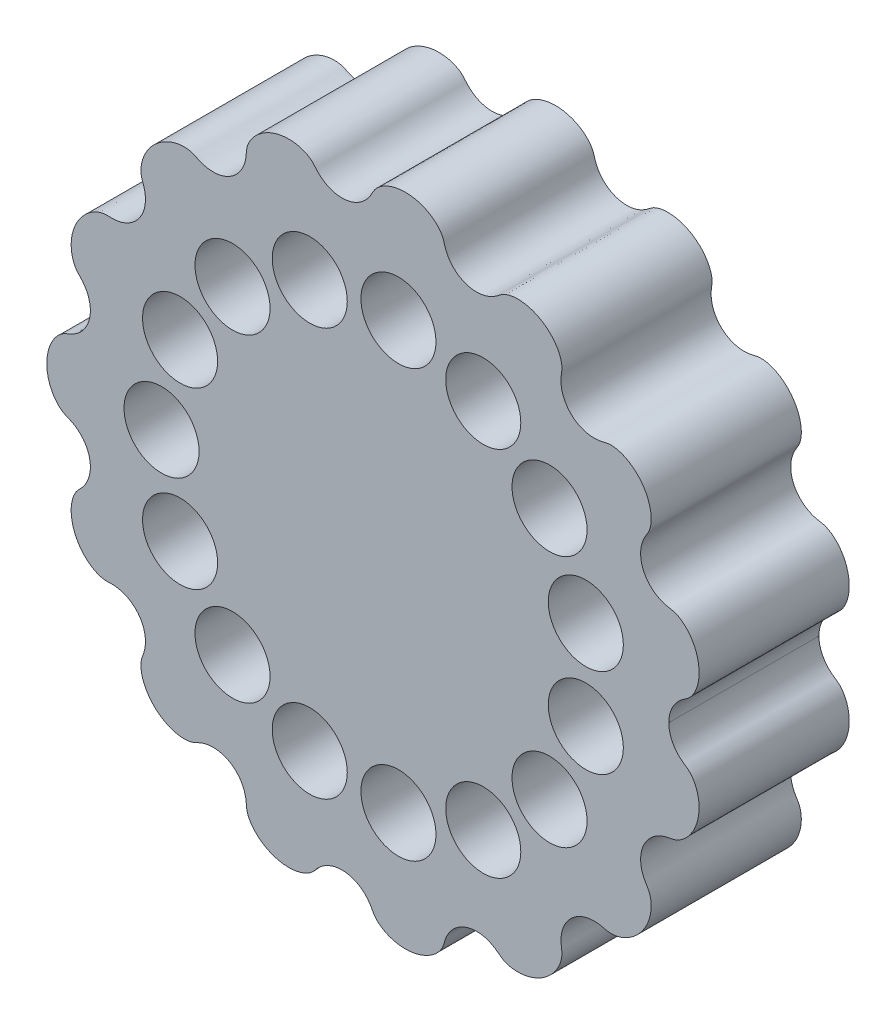
SolidWorks part; units mm, degrees
material "ABS"
ref_plane "Front Plane" through (0, 0, 0) normal (0, 0, 1) x (1, 0, 0)
ref_plane "Top Plane" through (0, 0, 0) normal (0, 1, 0) x (1, 0, 0)
ref_plane "Right Plane" through (0, 0, 0) normal (1, 0, 0) x (0, 0, -1)
sketch "Sketch2" plane through (0, 0, 0) normal (0, 0, 1) x (1, 0, 0)
  line L0 (0, 0) -> (18.3781, 0) construction
  line L1 (0, 0) -> (-12.7, 0) construction
  line L6 (0, 0) -> (-26.7529, 0) construction
  circle A0 centre (0, 0) radius 9
  circle A1 centre (-12.7, 0) radius 2.2225
  circle A10 centre (-11.602, 5.1656) radius 2.2225
  circle A11 centre (-8.498, 9.4379) radius 2.2225
  circle A12 centre (-3.9245, 12.0784) radius 2.2225
  circle A13 centre (1.3275, 12.6304) radius 2.2225
  circle A14 centre (6.35, 10.9985) radius 2.2225
  circle A15 centre (10.2745, 7.4649) radius 2.2225
  circle A16 centre (12.4225, 2.6405) radius 2.2225
  circle A17 centre (12.4225, -2.6405) radius 2.2225
  circle A18 centre (10.2745, -7.4649) radius 2.2225
  circle A19 centre (6.35, -10.9985) radius 2.2225
  circle A20 centre (1.3275, -12.6304) radius 2.2225
  circle A21 centre (-3.9245, -12.0784) radius 2.2225
  circle A22 centre (-8.498, -9.4379) radius 2.2225
  circle A23 centre (-11.602, -5.1656) radius 2.2225
  spline S0 degree 4 poles (18.7633, 4.8586) (18.8566, 4.6949) (19.0126, 4.3502) (19.1295, 3.8883) (19.146, 3.3193) (19.0772, 2.8818) (18.9864, 2.5766) (18.8762, 2.3288) (18.7622, 2.1358) (18.6445, 1.9821) (18.5309, 1.8645) (18.4127, 1.7724) (18.2984, 1.6976) (18.1631, 1.6053) (18.0131, 1.4864) (17.8313, 1.3119) (17.6678, 1.103) (17.5417, 0.8858) (17.4501, 0.6688) (17.4009, 0.5099) (17.3699, 0.3735) (17.3511, 0.2546) (17.3405, 0.1491) (17.3351, 0.0404) (17.335, -0.0379) (17.3404, -0.1482) (17.3511, -0.2558) (17.3711, -0.3808) (17.4057, -0.5292) (17.4608, -0.6993) (17.5431, -0.8835) (17.6435, -1.0585) (17.7605, -1.2214) (17.8868, -1.3648) (18.0188, -1.4893) (18.152, -1.5968) (18.284, -1.6887) (18.4068, -1.7677) (18.5101, -1.8484) (18.6114, -1.9469) (18.7103, -2.0649) (18.8119, -2.2151) (18.9788, -2.5318) (19.1284, -3.0222) (19.1691, -3.6778) (19.0197, -4.3616) (18.7658, -4.895) (18.5029, -5.2499) (18.2908, -5.4667) (18.0909, -5.625) (17.936, -5.7218) (17.7996, -5.7887) (17.6725, -5.8365) (17.5499, -5.8688) (17.4098, -5.8911) (17.2557, -5.9192) (17.0952, -5.96) (16.9297, -6.0153) (16.7182, -6.1072) (16.4691, -6.2552) (16.2082, -6.4745) (15.9606, -6.7851) (15.777, -7.1489) (15.6723, -7.5479) (15.6565, -7.9135) (15.698, -8.2228) (15.7641, -8.4609) (15.8302, -8.6338) (15.9057, -8.7908) (15.9865, -8.9326) (16.0678, -9.0566) (16.1353, -9.1714) (16.1945, -9.3026) (16.2418, -9.4503) (16.2782, -9.6273) (16.3107, -9.9874) (16.2563, -10.505) (16.0255, -11.1471) (15.5906, -11.7382) (15.1094, -12.1391) (14.6943, -12.3573) (14.4005, -12.4606) (14.1434, -12.5135) (13.9574, -12.5296) (13.7955, -12.524) (13.646, -12.4991) (13.511, -12.464) (13.3614, -12.4266) (13.1944, -12.3981) (13.0154, -12.381) (12.8253, -12.3797) (12.5738, -12.4026) (12.2655, -12.4754) (11.9355, -12.6193) (11.6068, -12.8541) (11.3394, -13.1429) (11.1399, -13.4677) (11.021, -13.7866) (10.9639, -14.0781) (10.9493, -14.3167) (10.9547, -14.4996) (10.9719, -14.6649) (10.9953, -14.8125) (11.0138, -14.9707) (11.0079, -15.1399) (10.9777, -15.3255) (10.9213, -15.5246) (10.826, -15.7601) (10.6793, -16.0232) (10.4202, -16.3707) (10.0022, -16.7545) (9.5088, -17.0394) (8.9674, -17.2095) (8.5368, -17.2602) (8.2356, -17.2556) (7.9841, -17.2204) (7.7834, -17.1697) (7.6075, -17.1031) (7.4581, -17.0235) (7.3304, -16.9284) (7.2142, -16.8343) (7.0797, -16.7369) (6.924, -16.6408) (6.7101, -16.534) (6.4291, -16.4378) (6.0935, -16.3813) (5.7124, -16.3917) (5.3285, -16.4789) (4.9609, -16.6461) (4.6712, -16.86) (4.454, -17.0906) (4.3085, -17.2969) (4.2145, -17.4622) (4.1399, -17.6257) (4.0811, -17.7846) (4.0386, -17.9329) (4.0016, -18.0673) (3.9484, -18.2093) (3.8722, -18.3523) (3.7653, -18.5053) (3.5909, -18.7015) (3.3546, -18.9043) (2.9581, -19.1547) (2.3703, -19.371) (1.6409, -19.4521) (0.9694, -19.3309) (0.494, -19.1192) (0.1984, -18.911) (0.0633, -18.791) (-0.0409, -18.6762) (-0.125, -18.5593) (-0.1906, -18.4434) (-0.2573, -18.311) (-0.3397, -18.1701) (-0.438, -18.0263) (-0.5547, -17.8825) (-0.7278, -17.7063) (-0.975, -17.5157) (-1.2995, -17.3465) (-1.6974, -17.2377) (-2.1042, -17.2148) (-2.4971, -17.274) (-2.8174, -17.3902) (-3.0701, -17.532) (-3.2554, -17.6692) (-3.3861, -17.7848) (-3.5017, -17.9035) (-3.6031, -18.0229) (-3.6924, -18.133) (-3.7817, -18.2231) (-3.8867, -18.3093) (-4.0128, -18.3939) (-4.1741, -18.4797) (-4.4111, -18.5737) (-4.7049, -18.6489) (-5.1436, -18.6992) (-5.7326, -18.6523) (-6.3023, -18.4708) (-6.8174, -18.1627) (-7.1549, -17.854) (-7.3507, -17.6166) (-7.4876, -17.3991) (-7.5669, -17.236) (-7.6196, -17.0913) (-7.6543, -16.9544) (-7.6725, -16.8247) (-7.6795, -16.6788) (-7.6932, -16.5185) (-7.7196, -16.3494) (-7.7615, -16.1729) (-7.8384, -15.9445) (-7.9726, -15.6719) (-8.1825, -15.3834) (-8.486, -15.1097) (-8.8424, -14.9039) (-9.2312, -14.778) (-9.586, -14.7404) (-9.8891, -14.7605) (-10.1254, -14.8081) (-10.2992, -14.8601) (-10.4589, -14.9217) (-10.6045, -14.9901) (-10.7343, -15.0569) (-10.8558, -15.106) (-10.9917, -15.1445) (-11.1433, -15.1711) (-11.3243, -15.184) (-11.5811, -15.1742) (-11.8846, -15.1233) (-12.3207, -14.9854) (-12.845, -14.6933) (-13.2871, -14.2907) (-13.6221, -13.8041) (-13.798, -13.399) (-13.8798, -13.107) (-13.9168, -12.8547) (-13.9232, -12.6721) (-13.913, -12.5206) (-13.8908, -12.3866) (-13.8575, -12.2643) (-13.8068, -12.1318) (-13.7541, -11.9843) (-13.7091, -11.8249) (-13.6743, -11.6539) (-13.6481, -11.4248) (-13.6517, -11.135) (-13.7112, -10.7995) (-13.8564, -10.4297) (-14.0796, -10.0888) (-14.3728, -9.7987) (-14.6815, -9.6022) (-14.9702, -9.4834) (-15.2094, -9.4216) (-15.3922, -9.3924) (-15.5659, -9.3793) (-15.7291, -9.3784) (-15.8771, -9.3868) (-16.0104, -9.3879) (-16.1536, -9.3736) (-16.3051, -9.3407) (-16.4766, -9.2837) (-16.8047, -9.1318) (-17.2258, -8.8259) (-17.6664, -8.3049) (-17.9609, -7.6328) (-18.0675, -7.0156) (-18.0489, -6.547) (-17.9914, -6.2409) (-17.9088, -5.9918) (-17.8296, -5.8227) (-17.7439, -5.6853) (-17.661, -5.5845) (-17.5943, -5.5141) (-17.5308, -5.4492) (-17.4724, -5.3879) (-17.4019, -5.309) (-17.3219, -5.2104) (-17.23, -5.0812) (-17.1338, -4.9172) (-17.0279, -4.688) (-16.9368, -4.3846) (-16.8964, -4.0268) (-16.9354, -3.6248) (-17.0518, -3.2488) (-17.2333, -2.9135) (-17.4501, -2.6512) (-17.6739, -2.4559) (-17.8733, -2.324) (-18.0344, -2.2373) (-18.1861, -2.1695) (-18.3256, -2.1159) (-18.4719, -2.0529) (-18.6155, -1.9632) (-18.7611, -1.8442) (-18.9053, -1.6958) (-19.0616, -1.4955) (-19.192, -1.2774) (-19.2944, -1.0552) (-19.3719, -0.8334) (-19.4214, -0.6522) (-19.4539, -0.4901) (-19.4739, -0.3535) (-19.4855, -0.2338) (-19.4917, -0.1326) (-19.4948, -0.037) (-19.4948, 0.0364) (-19.4917, 0.1316) (-19.4856, 0.232) (-19.4742, 0.351) (-19.4544, 0.4867) (-19.4225, 0.6475) (-19.3737, 0.8276) (-19.2973, 1.048) (-19.1964, 1.2688) (-19.0681, 1.4857) (-18.9143, 1.6852) (-18.7725, 1.8335) (-18.6329, 1.9498) (-18.5003, 2.0363) (-18.3706, 2.0977) (-18.2504, 2.1445) (-18.1062, 2.2036) (-17.9419, 2.2842) (-17.733, 2.4112) (-17.4958, 2.6047) (-17.2705, 2.8611) (-17.0558, 3.2276) (-16.9099, 3.6914) (-16.895, 4.0854) (-16.9436, 4.3777) (-16.984, 4.5249) knots 0 0 0 0 0 0.009284 0.018569 0.023211 0.027854 0.031033 0.034213 0.036543 0.038874 0.040556 0.042237 0.043918 0.0456 0.048628 0.051656 0.056303 0.058626 0.060948 0.063272 0.064433 0.065595 0.066886 0.068176 0.069432 0.070688 0.071943 0.073199 0.07572 0.07824 0.080694 0.083148 0.08563 0.088113 0.090095 0.092076 0.094058 0.09604 0.097282 0.098525 0.10101 0.103607 0.106204 0.116127 0.126049 0.135533 0.140274 0.145016 0.147725 0.150434 0.152813 0.154002 0.155191 0.157122 0.159052 0.160982 0.162912 0.165276 0.167641 0.172327 0.177141 0.181961 0.187087 0.192259 0.197312 0.199858 0.202403 0.204413 0.206423 0.208433 0.210443 0.211712 0.212982 0.21552 0.21806 0.2206 0.230761 0.24092 0.251197 0.256273 0.261349 0.26392 0.26649 0.269181 0.270527 0.271873 0.273958 0.276043 0.278128 0.280213 0.282806 0.285398 0.290549 0.295754 0.300413 0.305158 0.309821 0.314419 0.31708 0.319741 0.321582 0.323422 0.325263 0.327104 0.329419 0.331734 0.334508 0.337282 0.34191 0.346537 0.355792 0.365046 0.369673 0.374301 0.377075 0.379849 0.382164 0.384479 0.38632 0.388161 0.390001 0.391842 0.394503 0.397165 0.401762 0.406425 0.41117 0.415829 0.421034 0.426185 0.428777 0.43137 0.433455 0.43554 0.437625 0.439711 0.441056 0.442402 0.445093 0.447663 0.450234 0.45531 0.460386 0.470663 0.480822 0.490983 0.493523 0.496063 0.498601 0.499871 0.50114 0.50315 0.50516 0.50717 0.50918 0.511725 0.514271 0.519324 0.524496 0.529623 0.534442 0.539256 0.543942 0.546307 0.548671 0.550601 0.552531 0.554461 0.556392 0.557581 0.55877 0.561149 0.563858 0.566567 0.571309 0.57605 0.585534 0.595456 0.600418 0.605379 0.607976 0.610573 0.613058 0.614301 0.615543 0.617525 0.619507 0.621488 0.62347 0.625953 0.628436 0.633343 0.638384 0.643407 0.648429 0.653471 0.658378 0.660861 0.663343 0.665325 0.667307 0.669288 0.67127 0.672513 0.673755 0.676241 0.678838 0.681434 0.686396 0.691357 0.701279 0.710763 0.715505 0.720246 0.722955 0.725664 0.728043 0.729232 0.730422 0.732352 0.734282 0.736212 0.738142 0.740507 0.742871 0.747557 0.752371 0.757191 0.762317 0.76749 0.772543 0.775088 0.777634 0.779644 0.781654 0.783663 0.785673 0.786943 0.788212 0.790751 0.793291 0.79583 0.805991 0.816151 0.826427 0.831503 0.83658 0.83915 0.841721 0.844412 0.845757 0.847103 0.848145 0.849188 0.85023 0.851273 0.853358 0.855443 0.858036 0.860629 0.865779 0.870984 0.875643 0.880389 0.885051 0.889649 0.89231 0.894972 0.896812 0.898653 0.900493 0.902334 0.904649 0.906964 0.909738 0.912513 0.91714 0.919454 0.921767 0.924081 0.926394 0.927551 0.928708 0.929865 0.931022 0.93217 0.933319 0.934467 0.935616 0.937913 0.94021 0.942507 0.944804 0.949398 0.952146 0.954894 0.957192 0.95949 0.961079 0.962667 0.964255 0.965844 0.968759 0.971674 0.976278 0.980873 0.985473 0.99248 1 1 1 1 1 construction
  spline S1 degree 4 poles (17.3355, 0) (17.3355, -0.022) (17.3364, -0.0661) (17.3404, -0.1482) (17.3511, -0.2558) (17.3711, -0.3808) (17.4057, -0.5292) (17.4608, -0.6993) (17.5431, -0.8835) (17.6435, -1.0585) (17.7605, -1.2214) (17.8868, -1.3648) (18.0188, -1.4893) (18.152, -1.5968) (18.284, -1.6887) (18.4068, -1.7677) (18.5101, -1.8484) (18.6114, -1.9469) (18.7103, -2.0649) (18.8119, -2.2151) (18.9788, -2.5318) (19.1284, -3.0222) (19.1691, -3.6778) (19.0197, -4.3616) (18.7658, -4.895) (18.5029, -5.2499) (18.2908, -5.4667) (18.0909, -5.625) (17.936, -5.7218) (17.7996, -5.7887) (17.6725, -5.8365) (17.5499, -5.8688) (17.4098, -5.8911) (17.2557, -5.9192) (17.0952, -5.96) (16.9297, -6.0153) (16.7182, -6.1072) (16.4691, -6.2552) (16.2082, -6.4745) (15.9606, -6.7851) (15.777, -7.1489) (15.6723, -7.5479) (15.6565, -7.9135) (15.698, -8.2228) (15.7641, -8.4609) (15.8302, -8.6338) (15.9057, -8.7908) (15.9865, -8.9326) (16.0678, -9.0566) (16.1353, -9.1714) (16.1945, -9.3026) (16.2418, -9.4503) (16.2782, -9.6273) (16.3107, -9.9874) (16.2563, -10.505) (16.0255, -11.1471) (15.5906, -11.7382) (15.1094, -12.1391) (14.6943, -12.3573) (14.4005, -12.4606) (14.1434, -12.5135) (13.9574, -12.5296) (13.7955, -12.524) (13.646, -12.4991) (13.511, -12.464) (13.3614, -12.4266) (13.1944, -12.3981) (13.0154, -12.381) (12.8253, -12.3797) (12.5738, -12.4026) (12.2655, -12.4754) (11.9355, -12.6193) (11.6068, -12.8541) (11.3394, -13.1429) (11.1399, -13.4677) (11.021, -13.7866) (10.9639, -14.0781) (10.9493, -14.3167) (10.9547, -14.4996) (10.9719, -14.6649) (10.9953, -14.8125) (11.0138, -14.9707) (11.0079, -15.1399) (10.9777, -15.3255) (10.9213, -15.5246) (10.826, -15.7601) (10.6793, -16.0232) (10.4202, -16.3707) (10.0022, -16.7545) (9.5088, -17.0394) (8.9674, -17.2095) (8.5368, -17.2602) (8.2356, -17.2556) (7.9841, -17.2204) (7.7834, -17.1697) (7.6075, -17.1031) (7.4581, -17.0235) (7.3304, -16.9284) (7.2142, -16.8343) (7.0797, -16.7369) (6.924, -16.6408) (6.7101, -16.534) (6.4291, -16.4378) (6.0935, -16.3813) (5.7124, -16.3917) (5.3285, -16.4789) (4.9609, -16.6461) (4.6712, -16.86) (4.454, -17.0906) (4.3085, -17.2969) (4.2145, -17.4622) (4.1399, -17.6257) (4.0811, -17.7846) (4.0386, -17.9329) (4.0016, -18.0673) (3.9484, -18.2093) (3.8722, -18.3523) (3.7653, -18.5053) (3.5909, -18.7015) (3.3546, -18.9043) (2.9581, -19.1547) (2.3703, -19.371) (1.6409, -19.4521) (0.9694, -19.3309) (0.494, -19.1192) (0.1984, -18.911) (0.0633, -18.791) (-0.0409, -18.6762) (-0.125, -18.5593) (-0.1906, -18.4434) (-0.2573, -18.311) (-0.3397, -18.1701) (-0.438, -18.0263) (-0.5547, -17.8825) (-0.7278, -17.7063) (-0.975, -17.5157) (-1.2995, -17.3465) (-1.6974, -17.2377) (-2.1042, -17.2148) (-2.4971, -17.274) (-2.8174, -17.3902) (-3.0701, -17.532) (-3.2554, -17.6692) (-3.3861, -17.7848) (-3.5017, -17.9035) (-3.6031, -18.0229) (-3.6924, -18.133) (-3.7817, -18.2231) (-3.8867, -18.3093) (-4.0128, -18.3939) (-4.1741, -18.4797) (-4.4111, -18.5737) (-4.7049, -18.6489) (-5.1436, -18.6992) (-5.7326, -18.6523) (-6.3023, -18.4708) (-6.8174, -18.1627) (-7.1549, -17.854) (-7.3507, -17.6166) (-7.4876, -17.3991) (-7.5669, -17.236) (-7.6196, -17.0913) (-7.6543, -16.9544) (-7.6725, -16.8247) (-7.6795, -16.6788) (-7.6932, -16.5185) (-7.7196, -16.3494) (-7.7615, -16.1729) (-7.8384, -15.9445) (-7.9726, -15.6719) (-8.1825, -15.3834) (-8.486, -15.1097) (-8.8424, -14.9039) (-9.2312, -14.778) (-9.586, -14.7404) (-9.8891, -14.7605) (-10.1254, -14.8081) (-10.2992, -14.8601) (-10.4589, -14.9217) (-10.6045, -14.9901) (-10.7343, -15.0569) (-10.8558, -15.106) (-10.9917, -15.1445) (-11.1433, -15.1711) (-11.3243, -15.184) (-11.5811, -15.1742) (-11.8846, -15.1233) (-12.3207, -14.9854) (-12.845, -14.6933) (-13.2871, -14.2907) (-13.6221, -13.8041) (-13.798, -13.399) (-13.8798, -13.107) (-13.9168, -12.8547) (-13.9232, -12.6721) (-13.913, -12.5206) (-13.8908, -12.3866) (-13.8575, -12.2643) (-13.8068, -12.1318) (-13.7541, -11.9843) (-13.7091, -11.8249) (-13.6743, -11.6539) (-13.6481, -11.4248) (-13.6517, -11.135) (-13.7112, -10.7995) (-13.8564, -10.4297) (-14.0796, -10.0888) (-14.3728, -9.7987) (-14.6815, -9.6022) (-14.9702, -9.4834) (-15.2094, -9.4216) (-15.3922, -9.3924) (-15.5659, -9.3793) (-15.7291, -9.3784) (-15.8771, -9.3868) (-16.0104, -9.3879) (-16.1536, -9.3736) (-16.3051, -9.3407) (-16.4766, -9.2837) (-16.8047, -9.1318) (-17.2258, -8.8259) (-17.6664, -8.3049) (-17.9609, -7.6328) (-18.0675, -7.0156) (-18.0489, -6.547) (-17.9914, -6.2409) (-17.9088, -5.9918) (-17.8296, -5.8227) (-17.7439, -5.6853) (-17.661, -5.5845) (-17.5943, -5.5141) (-17.5308, -5.4492) (-17.4724, -5.3879) (-17.4019, -5.309) (-17.3219, -5.2104) (-17.23, -5.0812) (-17.1338, -4.9172) (-17.0279, -4.688) (-16.9368, -4.3846) (-16.8964, -4.0268) (-16.9354, -3.6248) (-17.0518, -3.2488) (-17.2333, -2.9135) (-17.4501, -2.6512) (-17.6739, -2.4559) (-17.8733, -2.324) (-18.0344, -2.2373) (-18.1861, -2.1695) (-18.3256, -2.1159) (-18.4719, -2.0529) (-18.6155, -1.9632) (-18.7611, -1.8442) (-18.9053, -1.6958) (-19.0616, -1.4955) (-19.192, -1.2774) (-19.2944, -1.0552) (-19.3719, -0.8334) (-19.4214, -0.6522) (-19.4539, -0.4901) (-19.4739, -0.3535) (-19.4855, -0.2338) (-19.4917, -0.1326) (-19.494, -0.0608) (-19.4945, -0.0203) (-19.4945, 0) knots 0.068176 0.068176 0.068176 0.068176 0.068176 0.069432 0.070688 0.071943 0.073199 0.07572 0.07824 0.080694 0.083148 0.08563 0.088113 0.090095 0.092076 0.094058 0.09604 0.097282 0.098525 0.10101 0.103607 0.106204 0.116127 0.126049 0.135533 0.140274 0.145016 0.147725 0.150434 0.152813 0.154002 0.155191 0.157122 0.159052 0.160982 0.162912 0.165276 0.167641 0.172327 0.177141 0.181961 0.187087 0.192259 0.197312 0.199858 0.202403 0.204413 0.206423 0.208433 0.210443 0.211712 0.212982 0.21552 0.21806 0.2206 0.230761 0.24092 0.251197 0.256273 0.261349 0.26392 0.26649 0.269181 0.270527 0.271873 0.273958 0.276043 0.278128 0.280213 0.282806 0.285398 0.290549 0.295754 0.300413 0.305158 0.309821 0.314419 0.31708 0.319741 0.321582 0.323422 0.325263 0.327104 0.329419 0.331734 0.334508 0.337282 0.34191 0.346537 0.355792 0.365046 0.369673 0.374301 0.377075 0.379849 0.382164 0.384479 0.38632 0.388161 0.390001 0.391842 0.394503 0.397165 0.401762 0.406425 0.41117 0.415829 0.421034 0.426185 0.428777 0.43137 0.433455 0.43554 0.437625 0.439711 0.441056 0.442402 0.445093 0.447663 0.450234 0.45531 0.460386 0.470663 0.480822 0.490983 0.493523 0.496063 0.498601 0.499871 0.50114 0.50315 0.50516 0.50717 0.50918 0.511725 0.514271 0.519324 0.524496 0.529623 0.534442 0.539256 0.543942 0.546307 0.548671 0.550601 0.552531 0.554461 0.556392 0.557581 0.55877 0.561149 0.563858 0.566567 0.571309 0.57605 0.585534 0.595456 0.600418 0.605379 0.607976 0.610573 0.613058 0.614301 0.615543 0.617525 0.619507 0.621488 0.62347 0.625953 0.628436 0.633343 0.638384 0.643407 0.648429 0.653471 0.658378 0.660861 0.663343 0.665325 0.667307 0.669288 0.67127 0.672513 0.673755 0.676241 0.678838 0.681434 0.686396 0.691357 0.701279 0.710763 0.715505 0.720246 0.722955 0.725664 0.728043 0.729232 0.730422 0.732352 0.734282 0.736212 0.738142 0.740507 0.742871 0.747557 0.752371 0.757191 0.762317 0.76749 0.772543 0.775088 0.777634 0.779644 0.781654 0.783663 0.785673 0.786943 0.788212 0.790751 0.793291 0.79583 0.805991 0.816151 0.826427 0.831503 0.83658 0.83915 0.841721 0.844412 0.845757 0.847103 0.848145 0.849188 0.85023 0.851273 0.853358 0.855443 0.858036 0.860629 0.865779 0.870984 0.875643 0.880389 0.885051 0.889649 0.89231 0.894972 0.896812 0.898653 0.900493 0.902334 0.904649 0.906964 0.909738 0.912513 0.91714 0.919454 0.921767 0.924081 0.926394 0.927551 0.928708 0.929865 0.931022 0.931022 0.931022 0.931022 0.931022
  spline S2 degree 4 poles (17.3355, 0) (17.3355, 0.022) (17.3364, 0.0661) (17.3404, 0.1482) (17.3511, 0.2558) (17.3711, 0.3808) (17.4057, 0.5292) (17.4608, 0.6993) (17.5431, 0.8835) (17.6435, 1.0585) (17.7605, 1.2214) (17.8868, 1.3648) (18.0188, 1.4893) (18.152, 1.5968) (18.284, 1.6887) (18.4068, 1.7677) (18.5101, 1.8484) (18.6114, 1.9469) (18.7103, 2.0649) (18.8119, 2.2151) (18.9788, 2.5318) (19.1284, 3.0222) (19.1691, 3.6778) (19.0197, 4.3616) (18.7658, 4.895) (18.5029, 5.2499) (18.2908, 5.4667) (18.0909, 5.625) (17.936, 5.7218) (17.7996, 5.7887) (17.6725, 5.8365) (17.5499, 5.8688) (17.4098, 5.8911) (17.2557, 5.9192) (17.0952, 5.96) (16.9297, 6.0153) (16.7182, 6.1072) (16.4691, 6.2552) (16.2082, 6.4745) (15.9606, 6.7851) (15.777, 7.1489) (15.6723, 7.5479) (15.6565, 7.9135) (15.698, 8.2228) (15.7641, 8.4609) (15.8302, 8.6338) (15.9057, 8.7908) (15.9865, 8.9326) (16.0678, 9.0566) (16.1353, 9.1714) (16.1945, 9.3026) (16.2418, 9.4503) (16.2782, 9.6273) (16.3107, 9.9874) (16.2563, 10.505) (16.0255, 11.1471) (15.5906, 11.7382) (15.1094, 12.1391) (14.6943, 12.3573) (14.4005, 12.4606) (14.1434, 12.5135) (13.9574, 12.5296) (13.7955, 12.524) (13.646, 12.4991) (13.511, 12.464) (13.3614, 12.4266) (13.1944, 12.3981) (13.0154, 12.381) (12.8253, 12.3797) (12.5738, 12.4026) (12.2655, 12.4754) (11.9355, 12.6193) (11.6068, 12.8541) (11.3394, 13.1429) (11.1399, 13.4677) (11.021, 13.7866) (10.9639, 14.0781) (10.9493, 14.3167) (10.9547, 14.4996) (10.9719, 14.6649) (10.9953, 14.8125) (11.0138, 14.9707) (11.0079, 15.1399) (10.9777, 15.3255) (10.9213, 15.5246) (10.826, 15.7601) (10.6793, 16.0232) (10.4202, 16.3707) (10.0022, 16.7545) (9.5088, 17.0394) (8.9674, 17.2095) (8.5368, 17.2602) (8.2356, 17.2556) (7.9841, 17.2204) (7.7834, 17.1697) (7.6075, 17.1031) (7.4581, 17.0235) (7.3304, 16.9284) (7.2142, 16.8343) (7.0797, 16.7369) (6.924, 16.6408) (6.7101, 16.534) (6.4291, 16.4378) (6.0935, 16.3813) (5.7124, 16.3917) (5.3285, 16.4789) (4.9609, 16.6461) (4.6712, 16.86) (4.454, 17.0906) (4.3085, 17.2969) (4.2145, 17.4622) (4.1399, 17.6257) (4.0811, 17.7846) (4.0386, 17.9329) (4.0016, 18.0673) (3.9484, 18.2093) (3.8722, 18.3523) (3.7653, 18.5053) (3.5909, 18.7015) (3.3546, 18.9043) (2.9581, 19.1547) (2.3703, 19.371) (1.6409, 19.4521) (0.9694, 19.3309) (0.494, 19.1192) (0.1984, 18.911) (0.0633, 18.791) (-0.0409, 18.6762) (-0.125, 18.5593) (-0.1906, 18.4434) (-0.2573, 18.311) (-0.3397, 18.1701) (-0.438, 18.0263) (-0.5547, 17.8825) (-0.7278, 17.7063) (-0.975, 17.5157) (-1.2995, 17.3465) (-1.6974, 17.2377) (-2.1042, 17.2148) (-2.4971, 17.274) (-2.8174, 17.3902) (-3.0701, 17.532) (-3.2554, 17.6692) (-3.3861, 17.7848) (-3.5017, 17.9035) (-3.6031, 18.0229) (-3.6924, 18.133) (-3.7817, 18.2231) (-3.8867, 18.3093) (-4.0128, 18.3939) (-4.1741, 18.4797) (-4.4111, 18.5737) (-4.7049, 18.6489) (-5.1436, 18.6992) (-5.7326, 18.6523) (-6.3023, 18.4708) (-6.8174, 18.1627) (-7.1549, 17.854) (-7.3507, 17.6166) (-7.4876, 17.3991) (-7.5669, 17.236) (-7.6196, 17.0913) (-7.6543, 16.9544) (-7.6725, 16.8247) (-7.6795, 16.6788) (-7.6932, 16.5185) (-7.7196, 16.3494) (-7.7615, 16.1729) (-7.8384, 15.9445) (-7.9726, 15.6719) (-8.1825, 15.3834) (-8.486, 15.1097) (-8.8424, 14.9039) (-9.2312, 14.778) (-9.586, 14.7404) (-9.8891, 14.7605) (-10.1254, 14.8081) (-10.2992, 14.8601) (-10.4589, 14.9217) (-10.6045, 14.9901) (-10.7343, 15.0569) (-10.8558, 15.106) (-10.9917, 15.1445) (-11.1433, 15.1711) (-11.3243, 15.184) (-11.5811, 15.1742) (-11.8846, 15.1233) (-12.3207, 14.9854) (-12.845, 14.6933) (-13.2871, 14.2907) (-13.6221, 13.8041) (-13.798, 13.399) (-13.8798, 13.107) (-13.9168, 12.8547) (-13.9232, 12.6721) (-13.913, 12.5206) (-13.8908, 12.3866) (-13.8575, 12.2643) (-13.8068, 12.1318) (-13.7541, 11.9843) (-13.7091, 11.8249) (-13.6743, 11.6539) (-13.6481, 11.4248) (-13.6517, 11.135) (-13.7112, 10.7995) (-13.8564, 10.4297) (-14.0796, 10.0888) (-14.3728, 9.7987) (-14.6815, 9.6022) (-14.9702, 9.4834) (-15.2094, 9.4216) (-15.3922, 9.3924) (-15.5659, 9.3793) (-15.7291, 9.3784) (-15.8771, 9.3868) (-16.0104, 9.3879) (-16.1536, 9.3736) (-16.3051, 9.3407) (-16.4766, 9.2837) (-16.8047, 9.1318) (-17.2258, 8.8259) (-17.6664, 8.3049) (-17.9609, 7.6328) (-18.0675, 7.0156) (-18.0489, 6.547) (-17.9914, 6.2409) (-17.9088, 5.9918) (-17.8296, 5.8227) (-17.7439, 5.6853) (-17.661, 5.5845) (-17.5943, 5.5141) (-17.5308, 5.4492) (-17.4724, 5.3879) (-17.4019, 5.309) (-17.3219, 5.2104) (-17.23, 5.0812) (-17.1338, 4.9172) (-17.0279, 4.688) (-16.9368, 4.3846) (-16.8964, 4.0268) (-16.9354, 3.6248) (-17.0518, 3.2488) (-17.2333, 2.9135) (-17.4501, 2.6512) (-17.6739, 2.4559) (-17.8733, 2.324) (-18.0344, 2.2373) (-18.1861, 2.1695) (-18.3256, 2.1159) (-18.4719, 2.0529) (-18.6155, 1.9632) (-18.7611, 1.8442) (-18.9053, 1.6958) (-19.0616, 1.4955) (-19.192, 1.2774) (-19.2944, 1.0552) (-19.3719, 0.8334) (-19.4214, 0.6522) (-19.4539, 0.4901) (-19.4739, 0.3535) (-19.4855, 0.2338) (-19.4917, 0.1326) (-19.494, 0.0608) (-19.4945, 0.0203) (-19.4945, 0) knots 0.068176 0.068176 0.068176 0.068176 0.068176 0.069432 0.070688 0.071943 0.073199 0.07572 0.07824 0.080694 0.083148 0.08563 0.088113 0.090095 0.092076 0.094058 0.09604 0.097282 0.098525 0.10101 0.103607 0.106204 0.116127 0.126049 0.135533 0.140274 0.145016 0.147725 0.150434 0.152813 0.154002 0.155191 0.157122 0.159052 0.160982 0.162912 0.165276 0.167641 0.172327 0.177141 0.181961 0.187087 0.192259 0.197312 0.199858 0.202403 0.204413 0.206423 0.208433 0.210443 0.211712 0.212982 0.21552 0.21806 0.2206 0.230761 0.24092 0.251197 0.256273 0.261349 0.26392 0.26649 0.269181 0.270527 0.271873 0.273958 0.276043 0.278128 0.280213 0.282806 0.285398 0.290549 0.295754 0.300413 0.305158 0.309821 0.314419 0.31708 0.319741 0.321582 0.323422 0.325263 0.327104 0.329419 0.331734 0.334508 0.337282 0.34191 0.346537 0.355792 0.365046 0.369673 0.374301 0.377075 0.379849 0.382164 0.384479 0.38632 0.388161 0.390001 0.391842 0.394503 0.397165 0.401762 0.406425 0.41117 0.415829 0.421034 0.426185 0.428777 0.43137 0.433455 0.43554 0.437625 0.439711 0.441056 0.442402 0.445093 0.447663 0.450234 0.45531 0.460386 0.470663 0.480822 0.490983 0.493523 0.496063 0.498601 0.499871 0.50114 0.50315 0.50516 0.50717 0.50918 0.511725 0.514271 0.519324 0.524496 0.529623 0.534442 0.539256 0.543942 0.546307 0.548671 0.550601 0.552531 0.554461 0.556392 0.557581 0.55877 0.561149 0.563858 0.566567 0.571309 0.57605 0.585534 0.595456 0.600418 0.605379 0.607976 0.610573 0.613058 0.614301 0.615543 0.617525 0.619507 0.621488 0.62347 0.625953 0.628436 0.633343 0.638384 0.643407 0.648429 0.653471 0.658378 0.660861 0.663343 0.665325 0.667307 0.669288 0.67127 0.672513 0.673755 0.676241 0.678838 0.681434 0.686396 0.691357 0.701279 0.710763 0.715505 0.720246 0.722955 0.725664 0.728043 0.729232 0.730422 0.732352 0.734282 0.736212 0.738142 0.740507 0.742871 0.747557 0.752371 0.757191 0.762317 0.76749 0.772543 0.775088 0.777634 0.779644 0.781654 0.783663 0.785673 0.786943 0.788212 0.790751 0.793291 0.79583 0.805991 0.816151 0.826427 0.831503 0.83658 0.83915 0.841721 0.844412 0.845757 0.847103 0.848145 0.849188 0.85023 0.851273 0.853358 0.855443 0.858036 0.860629 0.865779 0.870984 0.875643 0.880389 0.885051 0.889649 0.89231 0.894972 0.896812 0.898653 0.900493 0.902334 0.904649 0.906964 0.909738 0.912513 0.91714 0.919454 0.921767 0.924081 0.926394 0.927551 0.928708 0.929865 0.931022 0.931022 0.931022 0.931022 0.931022
  dimension "D1" = 18
  dimension "D2" = 4.445
  dimension "D3" = 12.7
  dimension "D4" = 15
  dimension "D5" = 12.7
extrude "Boss-Extrude1" add sketch "Sketch2" along normal blind 8.89
sketch "Sketch3" plane through (0, 0, 8.89) normal (0, 0, 1) x (1, 0, 0)
  circle A0 centre (0, 0) radius 9
  circle A1 centre (0, 0) radius 9 construction
extrude "Boss-Extrude2" add sketch "Sketch3" against normal offset from surface (4.89 mm away) 4 up to face at (-1.0795, 0, 0)
